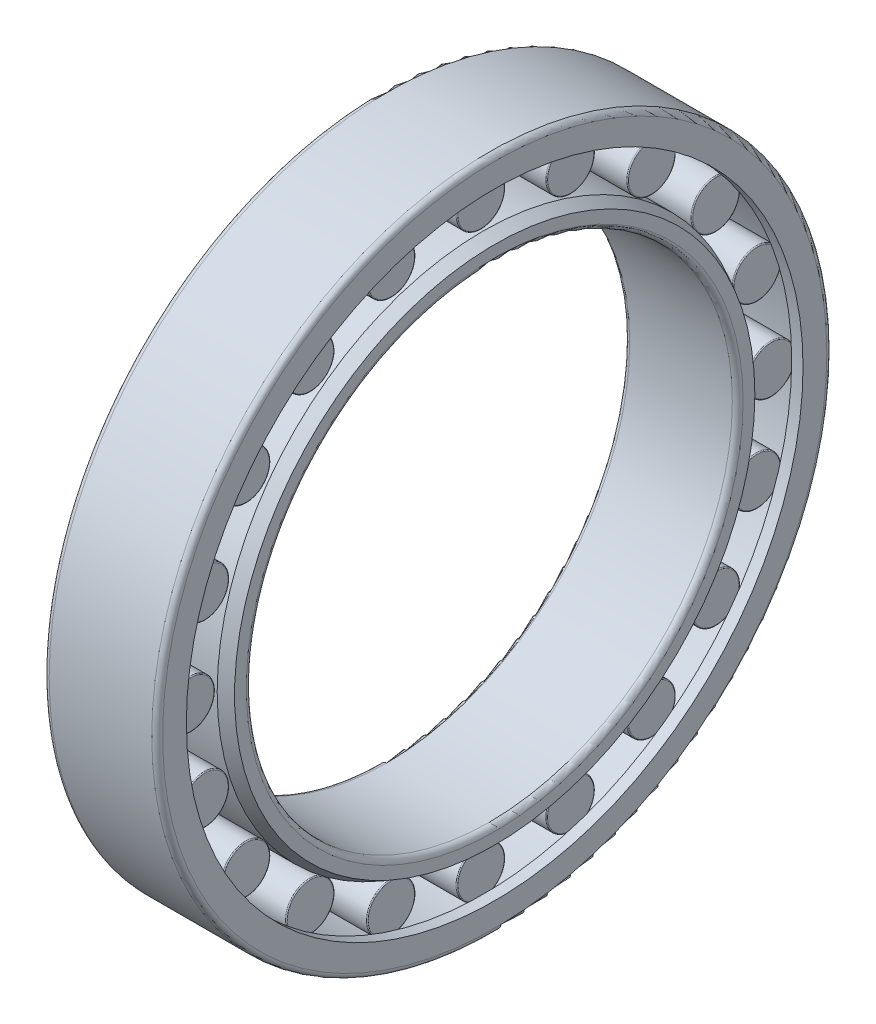
SolidWorks part; units mm, degrees
ref_plane "Plane1" through (0, 0, 0) normal (0, 0, 1) x (1, 0, 0)
ref_plane "Plane2" through (0, 0, 0) normal (0, 1, 0) x (1, 0, 0)
ref_plane "Plane3" through (0, 0, 0) normal (1, 0, 0) x (0, 0, -1)
sketch "Clipboard" plane through (0, 0, 0) normal (0, 0, 1) x (1, 0, 0)
  line L0 (-10, 0) -> (10, 0) construction
  line L1 (0, 0) -> (185.2698, -67.4327)
  line L2 (0, 0) -> (101.017, 36.7672)
  line L3 (0, 0) -> (218.798, -79.636)
  line L4 (0, 0) -> (-22.3471, -0.7804)
  dimension "Race_OD" = 232.84
  dimension "Race_ID" = 197.16
sketch "OutRacSke" plane through (0, 0, 0) normal (0, 0, 1) x (1, 0, 0)
  line L0 (-16.8, 114.1887) -> (-21, 114.1887)
  line L1 (-21, 114.1887) -> (-21, 123)
  line L2 (-19, 125) -> (19, 125)
  line L3 (21, 123) -> (21, 114.1888)
  line L4 (21, 114.1888) -> (16.8, 114.1888)
  line L5 (16.8, 114.1888) -> (16.8, 116.42)
  line L6 (16.8, 116.42) -> (-16.8, 116.42)
  line L7 (-16.8, 116.42) -> (-16.8, 114.1887)
  line L8 (-90, 0) -> (90, 0) construction
  arc A0 (-21, 123) -> (-19, 125) centre (-19, 123) cw
  arc A1 (19, 125) -> (21, 123) centre (19, 123) cw
  dimension "Race_OD" = 232.84
  dimension "radius" = 2
  dimension "groove_dp" = 2.2313
  dimension "Cyl_Len" = 33.6
revolve "OuterRace" add sketch "OutRacSke" angle 360 about L8 reverse direction yes
sketch "RolDetSke" plane through (0, 0, 0) normal (0, 0, 1) x (1, 0, 0)
  line L0 (-15.96, 116.068) -> (-15.96, 107.5)
  line L1 (-15.96, 107.5) -> (15.96, 107.5)
  line L2 (15.96, 107.5) -> (15.96, 116.068)
  line L3 (15.603, 116.425) -> (-15.603, 116.425)
  line L4 (-33.6, 107.5) -> (33.6, 107.5) construction
  arc A0 (15.96, 116.068) -> (15.603, 116.425) centre (15.603, 116.068) ccw
  arc A1 (-15.603, 116.425) -> (-15.96, 116.068) centre (-15.603, 116.068) ccw
  dimension "radius" = 0.357
  dimension "Roller_diameter" = 17.85
  dimension "halfLength" = 15.96
revolve "RollerDetailed" add sketch "RolDetSke" angle 360 about L4 reverse direction yes
ref_axis "Axis1" through (-50, 0, 0) along (1, 0, 0)
sketch "RolSimSke" plane through (0, 101.6, 0) normal (0, 0, 1) x (1, 0, 0)
  line L0 (-15.96, 14.468) -> (-15.96, -2.668)
  line L1 (25.4, -101.6) -> (-25.4, -101.6) construction
  line L2 (15.96, -2.668) -> (15.96, 14.468)
  line L3 (15.603, 14.825) -> (-15.603, 14.825)
  line L5 (15.603, -3.025) -> (-15.603, -3.025)
  arc A0 (15.96, 14.468) -> (15.603, 14.825) centre (15.603, 14.468) ccw
  arc A1 (-15.603, 14.825) -> (-15.96, 14.468) centre (-15.603, 14.468) ccw
  arc A2 (15.96, -2.668) -> (15.603, -3.025) centre (15.603, -2.668) cw
  arc A3 (-15.603, -3.025) -> (-15.96, -2.668) centre (-15.603, -2.668) cw
  dimension "radius" = 0.357
  dimension "D1" = 98.575
  dimension "Roller_diameter" = 17.85
  dimension "halfLength" = 15.96
revolve "RollersSimplified" [suppressed] add sketch "RolSimSke" angle 360 about L1
sketch "InsRacSke" plane through (0, 0, 0) normal (0, 0, 1) x (1, 0, 0)
  line L0 (-16.8, 98.58) -> (-21, 96.3487)
  line L1 (-21, 96.3487) -> (-21, 92)
  line L2 (-19, 90) -> (19, 90)
  line L3 (21, 92) -> (21, 96.3487)
  line L4 (21, 96.3487) -> (16.8, 98.58)
  line L5 (16.8, 98.58) -> (-16.8, 98.58)
  line L6 (-90, 0) -> (90, 0) construction
  line L7 (0, 0) -> (0, 127) construction
  arc A0 (-21, 92) -> (-19, 90) centre (-19, 92) ccw
  arc A1 (19, 90) -> (21, 92) centre (19, 92) ccw
  dimension "radius" = 2
  dimension "Race_ID" = 197.16
  dimension "Width" = 42
  dimension "groove_dp" = 2.2313
  dimension "Cyl_Len" = 33.6
revolve "InnerRace" add sketch "InsRacSke" angle 360 about L6 reverse direction yes
pattern_circular "RollersDetailed" count 20 every 18 about axis through (-50, 0, 0) along (1, 0, 0) of "RollerDetailed"
sketch "CagSpiSke" plane through (0, 0, 0) normal (0, 0, 1) x (1, 0, 0)
  line L0 (18.9, 105.2687) -> (18.9, 109.7313)
  line L1 (18.9, 109.7313) -> (-18.9, 109.7313)
  line L2 (-18.9, 109.7313) -> (-18.9, 105.2687)
  line L3 (-18.9, 105.2687) -> (18.9, 105.2687)
  line L4 (-90, 0) -> (90, 0) construction
revolve "CageSpine" [suppressed] add sketch "CagSpiSke" angle 360 about L4
equation "\"CLdia@Clipboard\" =  ( \"Race_OD@Clipboard\" + \"Race_ID@Clipboard\" )  / 4"
equation "\"Race_OD@OutRacSke\" = \"Race_OD@Clipboard\""
equation "\"halfCylLen@OutRacSke\" = \"Cyl_Len@OutRacSke\" / 2"
equation "\"RolCLRad@RolDetSke\" = \"CLdia@Clipboard\""
equation "\"Roller_diameter@RolDetSke\" =  ( \"Race_OD@Clipboard\" - \"Race_ID@Clipboard\" )  / 2 + .01"
equation "\"Roller_diameter@RolSimSke\" =  ( \"Race_OD@Clipboard\" - \"Race_ID@Clipboard\" )  / 2 + .01"
equation "\"radius@RolDetSke\" = \"Roller_diameter@RolDetSke\" / 50"
equation "\"Length@RolDetSke\" = \"Cyl_Len@OutRacSke\" * .95"
equation "\"halfLength@RolDetSke\" = \"Length@RolDetSke\" / 2"
equation "\"thickness@CagSpiSke\"  = \"Roller_diameter@RolDetSke\" * 0.25"
equation "\"Cag_IR@CagSpiSke\" =  \"RolCLRad@RolDetSke\" * 2 - \"thickness@CagSpiSke\""
equation "\"Rol_Length@RolSimSke\" = \"Cyl_Len@OutRacSke\" * .95"
equation "\"halfLength@RolSimSke\" = \"Rol_Length@RolSimSke\" / 2"
equation "\"radius@RolSimSke\" = \"radius@RolDetSke\""
equation "\"D1@RolSimSke\" = \"CLdia@Clipboard\" -  ( \"Roller_diameter@RolSimSke\" / 2 ) "
equation "\"Max_count@Clipboard\" = int( 3.14159265 / atn(( \"Roller_diameter@RolDetSke\" / 2) / sqr( \"RolCLRad@RolDetSke\"  *  \"RolCLRad@RolDetSke\" - ( \"Roller_diameter@RolDetSke\" / 2) *  ( \"Roller_diameter@RolDetSke\" / 2))))"
equation "\"Max_count@Clipboard\" = ((sgn( \"Max_count@Clipboard\" - \"Count@Clipboard\" )-1)*( \"Max_count@Clipboard\" - \"Count@Clipboard\" ))/-2+ \"Count@Clipboard\""
equation "\"Count@RollersDetailed\" = int( \"Show_count@Clipboard\" ) "
equation "\"Count@RollersDetailed\" = ((sgn( \"Count@RollersDetailed\" - \"Max_count@Clipboard\" )-1)*( \"Count@RollersDetailed\" - \"Max_count@Clipboard\" ))/-2+ \"Max_count@Clipboard\""
equation "\"Count@RollersDetailed\" = ((sgn( \"Count@RollersDetailed\" - \"Min_count@Clipboard\" )+1)*( \"Count@RollersDetailed\" - \"Min_count@Clipboard\"))/2 +\"Min_count@Clipboard\""
equation "\"Angle@RollersDetailed\" = 360.0 / \"Max_count@Clipboard\""
equation "\"halfWidth@OutRacSke\" = \"Width@OutRacSke\" / 2"
equation "\"radius@InsRacSke\" = \"radius@OutRacSke\" "
equation "\"groove_dp@InsRacSke\" = \"groove_dp@OutRacSke\""
equation "\"Width@InsRacSke\" = \"Width@OutRacSke\""
equation "' \"halfWidth@InsRacSke\" = \"Width@OutRacSke\" / 2"
equation "\"Race_ID@InsRacSke\" = \"Race_ID@Clipboard\""
equation "\"Cyl_Len@InsRacSke\" = \"Cyl_Len@OutRacSke\""
equation "\"Angle@CageSpine\" =  \"Angle@RollersDetailed\" * ( \"Count@RollersDetailed\" -1 + int( \"Count@RollersDetailed\" / \"Max_count@Clipboard\" ) )  + 0.001 -  int( \"Count@RollersDetailed\" / \"Max_count@Clipboard\" ) * 0.001"
equation "\"Angle@CageSpine\" =  \"Angle@CageSpine\" * int( \"Min_count@Clipboard\" / 2) + int(1 / \"Min_count@Clipboard\")  * 0.001"
equation "\"width@CagSpiSke\" =   ( \"Width@InsRacSke\" + \"Cyl_Len@InsRacSke\" )  / 2"
equation "\"halfwidth@CagSpiSke\" = \"width@CagSpiSke\" / 2"
